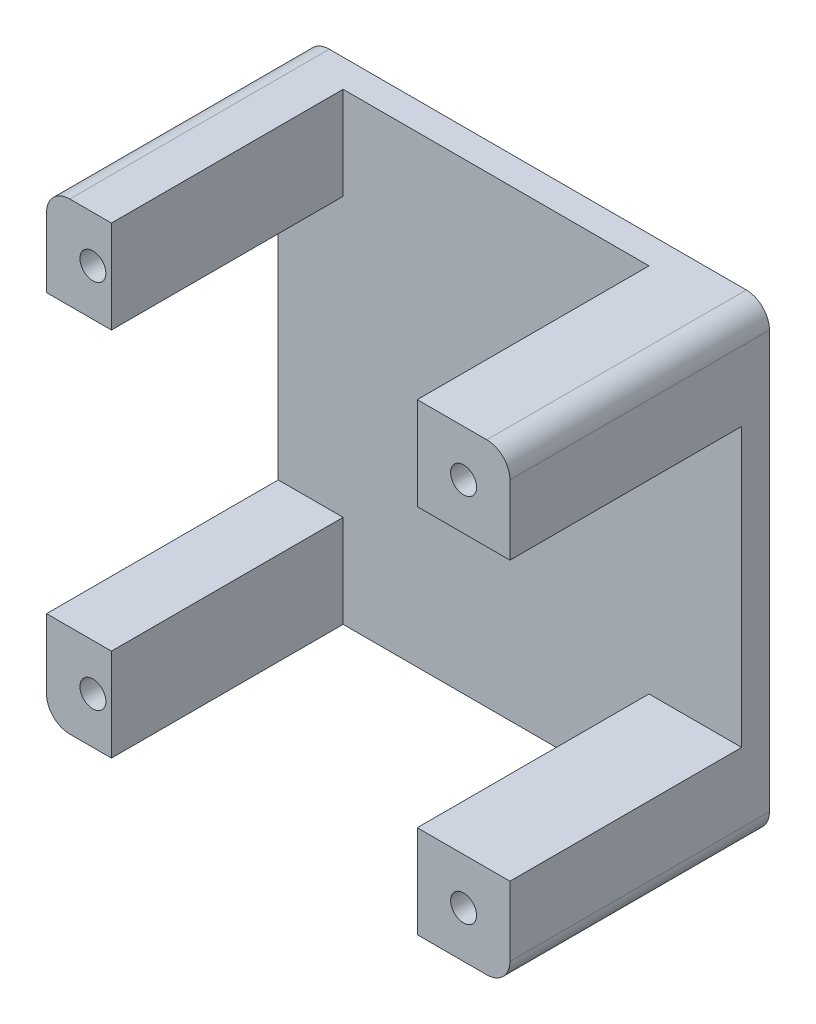
SolidWorks part; units mm, degrees
ref_plane "Front Plane" through (0, 0, 0) normal (0, 0, 1) x (1, 0, 0)
ref_plane "Top Plane" through (0, 0, 0) normal (0, 1, 0) x (1, 0, 0)
ref_plane "Right Plane" through (0, 0, 0) normal (1, 0, 0) x (0, 0, -1)
sketch "Sketch1" plane through (0, 0, 0) normal (0, 0, 1) x (1, 0, 0)
  line L0 (15, 15) -> (15, 9)
  line L1 (25, 9) -> (25, 15)
  line L2 (25, 15) -> (15, 15)
  line L3 (22.5, 25) -> (15, 25)
  line L4 (15, 25) -> (15, 15)
  line L5 (15, 15) -> (25, 15)
  line L6 (25, 15) -> (25, 22.5)
  line L7 (-25, 22.5) -> (-25, 15)
  line L8 (-25, 15) -> (-18, 15)
  line L9 (-18, 15) -> (-18, 25)
  line L10 (-18, 25) -> (-22.5, 25)
  line L11 (-18, 9) -> (-18, 15)
  line L12 (-18, 15) -> (-25, 15)
  line L13 (-25, 15) -> (-25, 9)
  line L14 (-18, -15) -> (-18, -9)
  line L15 (-25, -9) -> (-25, -15)
  line L16 (-25, -15) -> (-18, -15)
  line L17 (-22.5, -25) -> (-18, -25)
  line L18 (-18, -25) -> (-18, -15)
  line L19 (-18, -15) -> (-25, -15)
  line L20 (-25, -15) -> (-25, -22.5)
  line L21 (15, -9) -> (15, -15)
  line L22 (15, -15) -> (25, -15)
  line L23 (25, -15) -> (25, -9)
  line L24 (25, -22.5) -> (25, -15)
  line L25 (25, -15) -> (15, -15)
  line L26 (15, -15) -> (15, -25)
  line L27 (15, -25) -> (22.5, -25)
  line L28 (-25, 9) -> (-25, -9)
  line L29 (-18, -9) -> (-18, -25)
  line L30 (-18, -25) -> (15, -25)
  line L31 (15, -25) -> (15, -9)
  line L32 (25, -9) -> (25, 9)
  line L33 (15, 9) -> (15, 25)
  line L34 (15, 25) -> (-18, 25)
  line L35 (-18, 25) -> (-18, 9)
  line L36 (-18, 9) -> (-25, 9)
  line L37 (-25, 9) -> (-25, -9)
  line L38 (-25, -9) -> (-18, -9)
  line L39 (-18, -9) -> (-18, -25)
  line L40 (-18, -25) -> (15, -25)
  line L41 (15, -25) -> (15, -9)
  line L42 (15, -9) -> (25, -9)
  line L43 (25, -9) -> (25, 9)
  line L44 (25, 9) -> (15, 9)
  line L45 (15, 9) -> (15, 25)
  line L46 (15, 25) -> (-18, 25)
  line L47 (-18, 25) -> (-18, 9)
  circle A0 centre (20, 20) radius 1.4
  circle A1 centre (-20, 20) radius 1.4
  circle A2 centre (-20, -20) radius 1.4
  circle A3 centre (20, -20) radius 1.4
  arc A4 (25, 22.5) -> (22.5, 25) centre (22.5, 22.5) ccw
  arc A5 (-22.5, 25) -> (-25, 22.5) centre (-22.5, 22.5) ccw
  arc A6 (-25, -22.5) -> (-22.5, -25) centre (-22.5, -22.5) ccw
  arc A7 (22.5, -25) -> (25, -22.5) centre (22.5, -22.5) ccw
extrude "Boss-Extrude1" add sketch "Sketch1" along normal blind 3 contours L36 L11 L8 L13 | L32 L44 L0 L4 L34 L9 L11 L36 L28 L38 L14 L18 L30 L26 L21 L42 | L42 L21 L22 L23 | L44 L1 L2 L0 | L38 L15 L16 L14 region at (20, 12, 0) region at (-0.8098, 0, 0) region at (20, -12, 0) region at (-21.5, 12, 0) region at (-21.5, -12, 0)
extrude "Boss-Extrude2" add sketch "Sketch1<3>" along normal blind 28 contours L10 A5 L7 L8 L9 A1 | L20 A6 L17 L18 L16 A2 | L6 A4 L3 L4 L2 A0 | L27 A7 L24 L22 L26 A3 region at (15.1414, 20, 0) region at (-21.5847, 19.9047, 0) region at (24.8586, -18.75, 0) region at (-21.5847, -19.9047, 0)
sketch "Sketch1<3>" plane through (0, 0, 0) normal (0, 0, 1) x (1, 0, 0) same geometry as "Sketch1"
